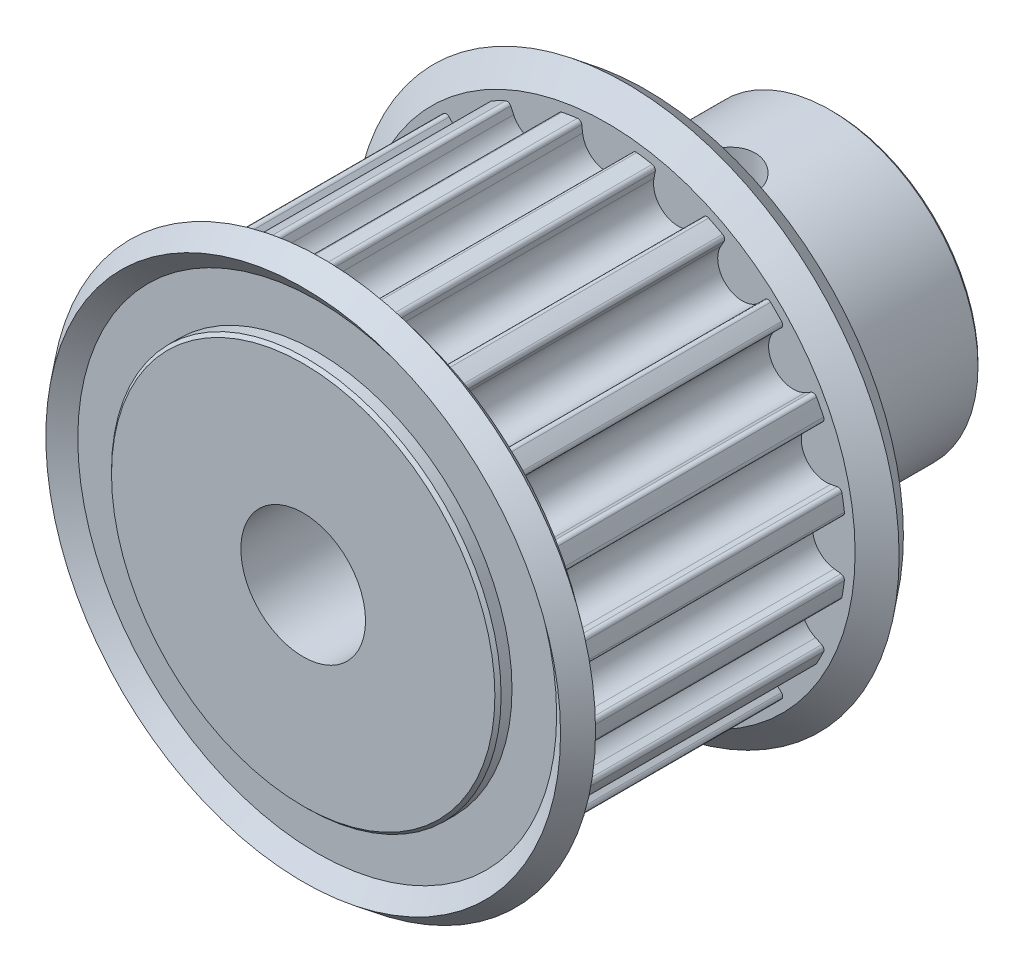
SolidWorks part; units mm, degrees
ref_plane "前视基准面" through (0, 0, 0) normal (0, 0, 1) x (1, 0, 0)
ref_plane "上视基准面" through (0, 0, 0) normal (0, 1, 0) x (1, 0, 0)
ref_plane "右视基准面" through (0, 0, 0) normal (1, 0, 0) x (0, 0, -1)
sketch "草图1" plane through (0, 0, 0) normal (1, 0, 0) x (0, 0, -1)
  line L0 (-34.7811, 0) -> (33.6192, 0) construction
  line L1 (0, 52.9736) -> (0, -62.0281) construction
  line L2 (-8.5, 15.345) -> (-8.5, 15.915)
  line L3 (-8.5, 15.915) -> (-9.7397, 17.5)
  line L4 (-9.7397, 17.5) -> (-11, 16.5143)
  line L5 (-11, 16.5143) -> (-10.1, 15.3636)
  line L6 (-10.1, 15.3636) -> (-10.1, 12.5)
  line L7 (-10.1, 12.5) -> (-11, 12.5)
  line L8 (10.1, 12.5) -> (11, 12.5)
  line L9 (10.1, 15.3636) -> (10.1, 12.5)
  line L10 (11, 16.5143) -> (10.1, 15.3636)
  line L11 (9.7397, 17.5) -> (11, 16.5143)
  line L12 (8.5, 15.915) -> (9.7397, 17.5)
  line L13 (8.5, 15.345) -> (8.5, 15.915)
  line L14 (8.5, -15.345) -> (8.5, -15.915)
  line L15 (8.5, -15.915) -> (9.7397, -17.5)
  line L16 (9.7397, -17.5) -> (11, -16.5143)
  line L17 (11, -16.5143) -> (10.1, -15.3636)
  line L18 (10.1, -15.3636) -> (10.1, -12.5)
  line L19 (10.1, -12.5) -> (11, -12.5)
  line L20 (-10.1, -12.5) -> (-11, -12.5)
  line L21 (-10.1, -15.3636) -> (-10.1, -12.5)
  line L22 (-11, -16.5143) -> (-10.1, -15.3636)
  line L23 (-9.7397, -17.5) -> (-11, -16.5143)
  line L24 (-8.5, -15.915) -> (-9.7397, -17.5)
  line L25 (-8.5, -15.345) -> (-8.5, -15.915)
  line L26 (-11, 12.5) -> (-11, -12.5)
  line L27 (11, 12.5) -> (11, -12.5)
  line L28 (-8.5, 15.345) -> (8.5, 15.345)
  line L29 (-8.5, -15.345) -> (8.5, -15.345)
  line L30 (11, 9.5) -> (23, 9.5)
  line L31 (11, -9.5) -> (23, -9.5)
  line L32 (23, 9.5) -> (23, -9.5)
  point P37 (16, 9.5)
  dimension "D1" = 2.5
  dimension "F" = 35
  dimension "D2" = 1.6
  dimension "E" = 25
  dimension "D3" = 1.6
  dimension "W" = 22
  dimension "D4" = 31.83
  dimension "A" = 17
  dimension "D5" = 30.69
  dimension "D6" = 7
  dimension "D" = 19
  dimension "L" = 34
sketch "草图2" plane through (0, 0, 0) normal (0, 0, 1) x (1, 0, 0)
  line L0 (-18.7064, 0) -> (19.5832, 0) construction
  line L1 (0, 30.5033) -> (0, -25.8377) construction
  line L2 (0, 0) -> (0, 15.345) construction
  line L3 (1.5718, 14.5756) -> (1.625, 15.0088)
  line L7 (0, 52.9736) -> (0, -62.0281) construction
  line L8 (-1.5, 3.7081) -> (-1.5, 5.4)
  line L9 (1.5, 3.7081) -> (1.5, 5.4)
  line L10 (-1.5, 5.4) -> (1.5, 5.4)
  line L11 (-1.5718, 14.5756) -> (-1.625, 15.0088)
  circle A0 centre (0, 0) radius 15.345
  circle A1 centre (0, 0) radius 15.915 construction
  circle A6 centre (0, 0) radius 2.5
  circle A7 centre (0, 0) radius 4
  arc A11 (-1.5718, 14.5756) -> (1.5718, 14.5756) centre (0, 14.7686) ccw
  arc A12 (-1.625, 15.0088) -> (-1.9042, 15.2264) centre (-1.8731, 14.9783) ccw
  arc A13 (1.625, 15.0088) -> (1.9042, 15.2264) centre (1.8731, 14.9783) cw
  point P7 (0, 15.915)
  point P8 (0, 15.345)
  point P13 (15.345, 0)
  dimension "PD" = 31.83
  dimension "OD" = 30.69
  dimension "H" = 5
  dimension "N" = 8
  dimension "D3" = 0.5
  dimension "D4" = 2.16
  dimension "D5" = 3.25
  dimension "D1" = 7
  dimension "b" = 3
  dimension "t" = 1.4
sketch "草图3" plane through (0, 0, 0) normal (1, 0, 0) x (0, 0, -1)
  line L0 (-11, 12.5) -> (-11, -12.5) construction
  line L1 (11, 12.5) -> (11, -12.5) construction
  line L2 (11, 16.5143) -> (10.1, 15.3636) construction
  line L3 (10.1, 12.5) -> (11, 12.5) construction
  line L4 (10.1, 15.3636) -> (10.1, 12.5) construction
  line L5 (-10.1, 15.3636) -> (-10.1, 12.5) construction
  line L6 (-11, 12.5) -> (-11, 0)
  line L7 (11, 12.5) -> (11, 0)
  line L8 (9.7397, 17.5) -> (11, 16.5143) construction
  line L9 (10.1, 12.5) -> (11, 12.5)
  line L10 (10.1, 15.3636) -> (10.1, 12.5)
  line L11 (-10.1, 15.3636) -> (-10.1, 12.5)
  line L12 (8.5, 15.915) -> (9.7397, 17.5) construction
  line L13 (8.5, 15.345) -> (8.5, 15.915) construction
  line L14 (-8.5, 15.345) -> (8.5, 15.345) construction
  line L15 (-8.5, 15.345) -> (-8.5, 15.915) construction
  line L16 (-8.5, 15.915) -> (-9.7397, 17.5) construction
  line L17 (-9.7397, 17.5) -> (-11, 16.5143) construction
  line L18 (-11, 16.5143) -> (-10.1, 15.3636) construction
  line L19 (11, 16.5143) -> (10.1, 15.3636)
  line L20 (9.7397, 17.5) -> (11, 16.5143)
  line L21 (8.5, 15.915) -> (9.7397, 17.5)
  line L22 (8.5, 15.345) -> (8.5, 15.915)
  line L23 (-8.5, 15.345) -> (8.5, 15.345)
  line L24 (-8.5, 15.345) -> (-8.5, 15.915)
  line L25 (-8.5, 15.915) -> (-9.7397, 17.5)
  line L26 (-9.7397, 17.5) -> (-11, 16.5143)
  line L27 (-11, 16.5143) -> (-10.1, 15.3636)
  line L28 (-34.7811, 0) -> (33.6192, 0) construction
  line L29 (-34.7811, 0) -> (33.6192, 0) construction
  line L30 (-11, 0) -> (11, 0)
  line L31 (-10.1, 12.5) -> (-11, 12.5) construction
  line L32 (-10.1, 12.5) -> (-11, 12.5)
revolve "旋转1" add sketch "草图3" angle 360 about L29
sketch "草图4" plane through (0, 0, 0) normal (0, 0, 1) x (1, 0, 0)
  line L3 (-1.5718, 14.5756) -> (-1.625, 15.0088) construction
  line L4 (1.5718, 14.5756) -> (1.625, 15.0088) construction
  line L5 (-1.5718, 14.5756) -> (-1.625, 15.0088)
  line L6 (1.5718, 14.5756) -> (1.625, 15.0088)
  circle A5 centre (0, 0) radius 15.345 construction
  arc A6 (-1.625, 15.0088) -> (-1.9042, 15.2264) centre (-1.8731, 14.9783) ccw construction
  arc A7 (-1.5718, 14.5756) -> (1.5718, 14.5756) centre (0, 14.7686) ccw construction
  arc A8 (1.9042, 15.2264) -> (1.625, 15.0088) centre (1.8731, 14.9783) ccw construction
  arc A9 (1.9042, 15.2264) -> (-1.9042, 15.2264) centre (0, 0) ccw
  arc A10 (-1.625, 15.0088) -> (-1.9042, 15.2264) centre (-1.8731, 14.9783) ccw
  arc A11 (-1.5718, 14.5756) -> (1.5718, 14.5756) centre (0, 14.7686) ccw
  arc A12 (1.9042, 15.2264) -> (1.625, 15.0088) centre (1.8731, 14.9783) ccw
extrude "切除-拉伸1" cut sketch "草图4" along normal up to vertex (8.5 mm away) from vertex up to point (0, 15.345, 8.5) starting at point (0, 15.345, -8.5)
pattern_circular "阵列(圆周)1" count 20 over 360 about axis through (0, 0, 34.7811) along (0, 0, 1) of "切除-拉伸1"
sketch "草图7" plane through (0, 0, 0) normal (1, 0, 0) x (0, 0, -1)
  line L0 (11, 9.5) -> (23, 9.5) construction
  line L1 (23, 9.5) -> (23, -9.5) construction
  line L2 (11, 12.5) -> (11, -12.5) construction
  line L3 (11, 9.5) -> (23, 9.5)
  line L4 (23, 9.5) -> (23, 0)
  line L5 (11, 9.5) -> (11, 0)
  line L6 (-34.7811, 0) -> (33.6192, 0) construction
  line L7 (-34.7811, 0) -> (33.6192, 0) construction
  line L8 (11, 0) -> (23, 0)
revolve "旋转2" add sketch "草图7" angle 360 about L7
sketch "草图5" plane through (0, 0, 0) normal (0, 0, 1) x (1, 0, 0)
  circle A0 centre (0, 0) radius 2.5 construction
  circle A1 centre (0, 0) radius 2.5
extrude "H" [suppressed] cut sketch "草图5" along normal up to vertex from vertex
sketch "草图6" plane through (0, 0, 0) normal (0, 0, 1) x (1, 0, 0)
  line L0 (-1.5, 5.4) -> (1.5, 5.4) construction
  line L1 (1.5, 3.7081) -> (1.5, 5.4) construction
  line L2 (-1.5, 3.7081) -> (-1.5, 5.4) construction
  line L3 (-1.5, 5.4) -> (1.5, 5.4)
  line L4 (1.5, 3.7081) -> (1.5, 5.4)
  line L5 (-1.5, 3.7081) -> (-1.5, 5.4)
  circle A0 centre (0, 0) radius 4 construction
  arc A1 (-1.5, 3.7081) -> (1.5, 3.7081) centre (0, 0) ccw
extrude "N" cut sketch "草图6" along normal up to vertex (11 mm away) from vertex up to point (0, 12.5, 11) starting at point (0, 9.5, -23)
sketch "草图9" plane through (0, 0, 0) normal (0, 0, 1) x (1, 0, 0)
  line L0 (-1.5, 3.7081) -> (-1.5, 5.4) construction
  line L1 (-1.5, 5.4) -> (1.5, 5.4) construction
  line L2 (1.5, 3.7081) -> (1.5, 5.4) construction
  line L3 (-1.5, 3.7081) -> (-1.5, 5.4)
  line L4 (-1.5, 5.4) -> (1.5, 5.4)
  line L5 (1.5, 3.7081) -> (1.5, 5.4)
  circle A0 centre (0, 0) radius 4 construction
  arc A1 (1.5, 3.7081) -> (-1.5, 3.7081) centre (0, 0) ccw
extrude "P" add sketch "草图9" along normal up to vertex from vertex up to point (0, 12.5, 11) starting at point (0, 9.5, -23)
sketch "草图8" plane through (0, 0, 0) normal (0, 1, 0) x (1, 0, 0)
  circle A0 centre (0, 16) radius 2
  dimension "M" = 4
extrude "螺纹孔1" cut sketch "草图8" along normal up to vertex up to point (0, 9.5, -16)
cosmetic thread "装饰螺纹线1" parameters "D2"=4.1
pattern_circular "螺纹孔2" count 2 every 120 about axis through (0, 0, 34.7811) along (0, 0, 1) of "螺纹孔1"
chamfer "倒角1" distance 0.2 angle 45 3 edges at (12.5, 0, -11) (12.5, 0, 11) (9.5, 0, -23)
